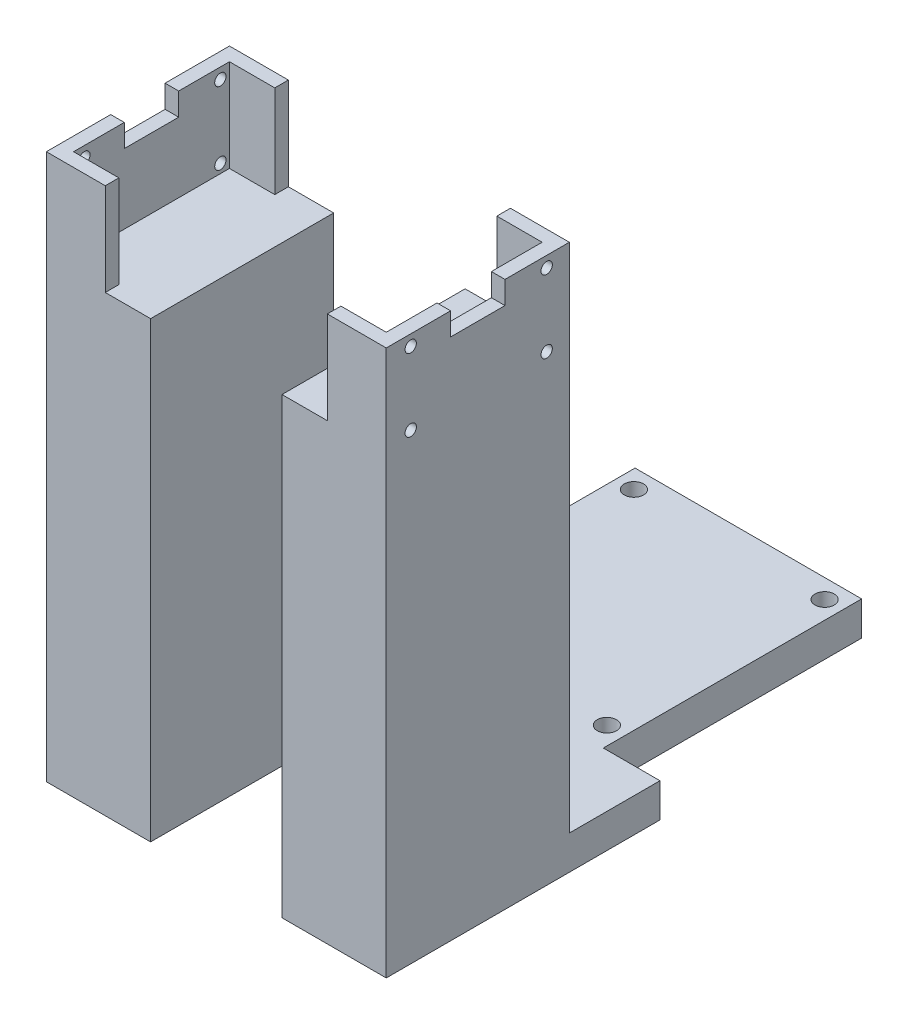
SolidWorks part; units mm, degrees
ref_plane "Front Plane" through (0, 0, 0) normal (0, 0, 1) x (1, 0, 0)
ref_plane "Top Plane" through (0, 0, 0) normal (0, 1, 0) x (1, 0, 0)
ref_plane "Right Plane" through (0, 0, 0) normal (1, 0, 0) x (0, 0, -1)
sketch "Sketch1" plane through (0, 0, 0) normal (0, 1, 0) x (1, 0, 0)
  line L0 (0, 110.0784) -> (0, -110.0784) construction
  line L1 (94.5305, 0) -> (-94.5305, 0) construction
  line L2 (-14.5, -17.2) -> (-14.5, 17.2)
  line L3 (-14.5, 17.2) -> (-34.5, 17.2)
  line L4 (-34.5, 17.2) -> (-34.5, -17.2)
  line L5 (-14.5, -17.2) -> (-34.5, -17.2)
  line L6 (14.5, -17.2) -> (34.5, -17.2)
  line L7 (34.5, 17.2) -> (34.5, -17.2)
  line L8 (14.5, 17.2) -> (34.5, 17.2)
  line L9 (14.5, -17.2) -> (14.5, 17.2)
  line L10 (-34.5, 17.2) -> (-37.5, 17.2)
  line L11 (-24.5, 17.2) -> (-24.5, 20.2)
  line L12 (-24.5, 20.2) -> (-37.5, 20.2)
  line L13 (-37.5, 20.2) -> (-37.5, -20.2)
  line L14 (-37.5, -20.2) -> (-24.5, -20.2)
  line L15 (-24.5, -20.2) -> (-24.5, -17.2)
  line L16 (-34.5, -17.2) -> (-37.5, -17.2)
  line L17 (-24.5, 20.2) -> (-14.5, 20.2)
  line L18 (-14.5, 20.2) -> (-14.5, -20.2)
  line L19 (-24.5, -20.2) -> (-14.5, -20.2)
  point P4 (0, 0)
  point P8 (0, 0)
  point P11 (-14.5, 0)
  point P14 (-34.5, 0)
  point P15 (-14.5, 0)
  point P19 (14.5, 0)
  point P20 (34.5, 0)
  dimension "D1" = 20
  dimension "D2" = 17.2
  dimension "D3" = 14.5
  dimension "D4" = 3
  dimension "D5" = 3
  dimension "D6" = 40.4
sketch "Sketch2" plane through (0, 0, 0) normal (1, 0, 0) x (0, 0, -1)
  line L0 (-17.2, 0) -> (-17.2, 20.4)
  line L1 (17.2, 0) -> (-17.2, 0) construction
  line L2 (-17.2, 20.4) -> (17.2, 20.4)
  line L3 (17.2, 20.4) -> (17.2, 0)
  line L4 (17.2, 0) -> (-17.2, 0)
  line L5 (-17.2, 10.2) -> (17.2, 10.2) construction
  line L6 (0, 0) -> (0, 20.4) construction
  circle A0 centre (-14.8, 18) radius 1.25
  circle A2 centre (-14.8, 2) radius 1.25
  circle A3 centre (15.2, 2) radius 1.25
  circle A4 centre (15.2, 18) radius 1.25
  dimension "D2" = 2.5
  dimension "D3" = 7.8
  dimension "D7" = 15.2
  dimension "D8" = 15.2
  dimension "D1" = 20.4
  dimension "D4" = 14.8
  dimension "D5" = 8.2
  dimension "D6" = 14.8
extrude "Boss-Extrude1" add sketch "Sketch2" against normal blind 3 from offset 34.5 offset against normal yes
extrude "Boss-Extrude2" add sketch "Sketch1" along normal up to surface (20.4 mm away) contours L14 L15 L5 L4 L10 L13 | L12 L13 L10 L3 L11 region at (-31, 0, 18.7) region at (-31, 0, -18.7) up to face at (-36, 20.4, 0)
extrude "Boss-Extrude3" add sketch "Sketch1<3>" against normal blind 3 contours L5 L2 L3 L4 | L15 L19 L18 L5 | L5 L16 L13 L14 L15 | L16 L4 L10 L13 | L12 L13 L10 L3 L11 | L18 L17 L11 L3 region at (-24.5, 0, 0) region at (-19.5, 0, 18.7) region at (-19.5, 0, -18.7) region at (-31, 0, 18.7) region at (-31, 0, -18.7) region at (-36, 0, 0)
sketch "Sketch1<3>" plane through (0, 0, 0) normal (0, 1, 0) x (1, 0, 0) same geometry as "Sketch1"
extrude "Boss-Extrude4" add sketch "Sketch1<4>" against normal blind 100 contours L16 L4 L10 L13 | L5 L16 L13 L14 L15 | L15 L19 L18 L5 | L5 L2 L3 L4 | L12 L13 L10 L3 L11 | L18 L17 L11 L3 region at (-24.5, 0, 0) region at (-19.5, 0, 18.7) region at (-19.5, 0, -18.7) region at (-31, 0, 18.7) region at (-31, 0, -18.7) region at (-36, 0, 0)
sketch "Sketch1<4>" plane through (0, 0, 0) normal (0, 1, 0) x (1, 0, 0) same geometry as "Sketch1"
sketch "Sketch4" plane through (-34.5, 0, 0) normal (1, 0, 0) x (0, 0, -1)
  line L0 (17.2, 20.4) -> (-17.2, 20.4) construction
  line L1 (-6, 25.4) -> (6, 25.4)
  line L2 (-6, 25.4) -> (-6, 15.4)
  line L3 (-6, 15.4) -> (6, 15.4)
  line L4 (6, 25.4) -> (6, 15.4)
  line L5 (0, 15.4) -> (0, 25.4) construction
  line L6 (-6, 20.4) -> (6, 20.4) construction
  point P0 (0, 20.4)
  dimension "D1" = 10
  dimension "D2" = 12
extrude "Cut-Extrude1" cut sketch "Sketch4" against normal blind 132
mirror "Mirror6" about plane through (0, 0, 0) normal (1, 0, 0) of bodies 107
ref_plane "Plane1" through (0, -100, 0) normal (0, 1, 0) x (1, 0, 0)
sketch "Sketch11" plane through (0, -100, 0) normal (0, 1, 0) x (1, 0, 0)
  line L1 (-50.3197, 46.5019) -> (50.3197, 46.5019)
  line L2 (-50.3197, 46.5019) -> (-50.3197, -46.5019)
  line L3 (-50.3197, -46.5019) -> (50.3197, -46.5019)
  line L4 (50.3197, 46.5019) -> (50.3197, -46.5019)
  line L5 (-50.3197, 46.5019) -> (50.3197, -46.5019) construction
  line L6 (-50.3197, -46.5019) -> (50.3197, 46.5019) construction
  circle A0 centre (0, 0) radius 12
  dimension "D1" = 24
sketch "Sketch7" plane through (0, -100, 0) normal (0, -1, 0) x (1, 0, 0)
  line L0 (-14.5, -20.2) -> (14.5, -20.2)
  line L1 (37.5, -20.2) -> (37.5, -40.2)
  line L2 (37.5, -40.2) -> (-37.5, -40.2)
  line L3 (-37.5, -40.2) -> (-37.5, -20.2)
  line L4 (14.5, -20.2) -> (37.5, -20.2) construction
  line L5 (-14.5, -20.2) -> (-37.5, -20.2) construction
  line L6 (14.5, -20.2) -> (37.5, -20.2)
  line L7 (-14.5, -20.2) -> (-37.5, -20.2)
  line L8 (-15, 47.5) -> (-15, 43.5) construction
  line L9 (-21, 47.5) -> (-21, 43.5) construction
  line L10 (21, 47.5) -> (21, 43.5) construction
  line L11 (15, 47.5) -> (15, 43.5) construction
  line L12 (-15, 47.5) -> (-15, 43.5)
  line L13 (-21, 47.5) -> (-21, 43.5)
  line L14 (21, 47.5) -> (21, 43.5)
  line L15 (15, 47.5) -> (15, 43.5)
  line L16 (-21.035, -44.95) -> (-21.035, -92.99) construction
  line L17 (-25, -40.2) -> (25, -40.2)
  line L18 (-25, -40.2) -> (-25, -97.2)
  line L19 (-25, -97.2) -> (25, -97.2)
  line L20 (25, -40.2) -> (25, -97.2)
  line L21 (-21.035, -92.99) -> (21.035, -92.99) construction
  arc A0 (-15, 47.5) -> (-21, 47.5) centre (-18, 47.5) ccw construction
  arc A1 (-21, 43.5) -> (-15, 43.5) centre (-18, 43.5) ccw construction
  arc A2 (21, 47.5) -> (15, 47.5) centre (18, 47.5) ccw construction
  arc A3 (15, 43.5) -> (21, 43.5) centre (18, 43.5) ccw construction
  arc A4 (-15, 47.5) -> (-21, 47.5) centre (-18, 47.5) ccw
  arc A5 (-21, 43.5) -> (-15, 43.5) centre (-18, 43.5) ccw
  arc A6 (21, 47.5) -> (15, 47.5) centre (18, 47.5) ccw
  arc A7 (15, 43.5) -> (21, 43.5) centre (18, 43.5) ccw
  circle A8 centre (-21.035, -44.95) radius 2.125
  circle A9 centre (-21.035, -92.99) radius 2.125
  circle A10 centre (21.035, -92.99) radius 2.125
  circle A11 centre (21.035, -44.95) radius 2.125
  point P23 (0, -97.2)
  point P36 (0, -92.99)
  line M4 (14.5, -20.2) -> (37.5, -20.2)
  dimension "D4" = 4.25
  dimension "D5" = 4.25
  dimension "D8" = 4.25
  dimension "D9" = 4.25
  dimension "D1" = 20
  dimension "D2" = 57
  dimension "D3" = 50
  dimension "D6" = 48.04
  dimension "D7" = 42.07
  dimension "D10" = 48.04
  dimension "D11" = 42.07
  dimension "D12" = 4.21
extrude "Boss-Extrude5" add sketch "Sketch7" against normal blind 7.5 contours L0 L7 L3 L2 L1 A7 L15 A6 L14 A5 L13 A4 L12 M4 | L20 L2 L18 L19 A11 A10 A9 A8 region at (0, -100, -30.2) region at (0, -100, -68.6945)
sketch "Sketch8" plane through (0, 0, 0) normal (0, 1, 0) x (1, 0, 0)
  line L0 (-47.2197, 74.2041) -> (9.7803, 74.2041)
  line L3 (-47.2197, 74.2041) -> (-47.2197, 26.2041)
  line L4 (-47.2197, 26.2041) -> (9.7803, 26.2041)
  line L5 (9.7803, 74.2041) -> (9.7803, 26.2041)
  circle A0 centre (7.2259, 71.2552) radius 2.125
  circle A1 centre (-40.8141, 71.2552) radius 2.125
  circle A2 centre (-40.8141, 29.1852) radius 2.125
  circle A3 centre (7.2259, 29.1852) radius 2.125
  dimension "D3" = 4.25
  dimension "D1" = 48.04
  dimension "D2" = 42.07
sketch "Sketch9" plane through (0, 0, 0) normal (0, 0, 1) x (1, 0, 0)
  line L0 (37.5, -26.283) -> (42.3357, -13.6761) construction
  line L1 (37.5, 20.4) -> (37.5, -100) construction
  line L2 (42.3357, -13.6761) -> (37.5, -13.6761) construction
  line L3 (37.5, -13.6761) -> (42.3357, -13.6761)
  line L4 (42.3357, -13.6761) -> (37.5, -26.283)
  line L5 (37.5, -26.283) -> (37.5, -13.6761)
